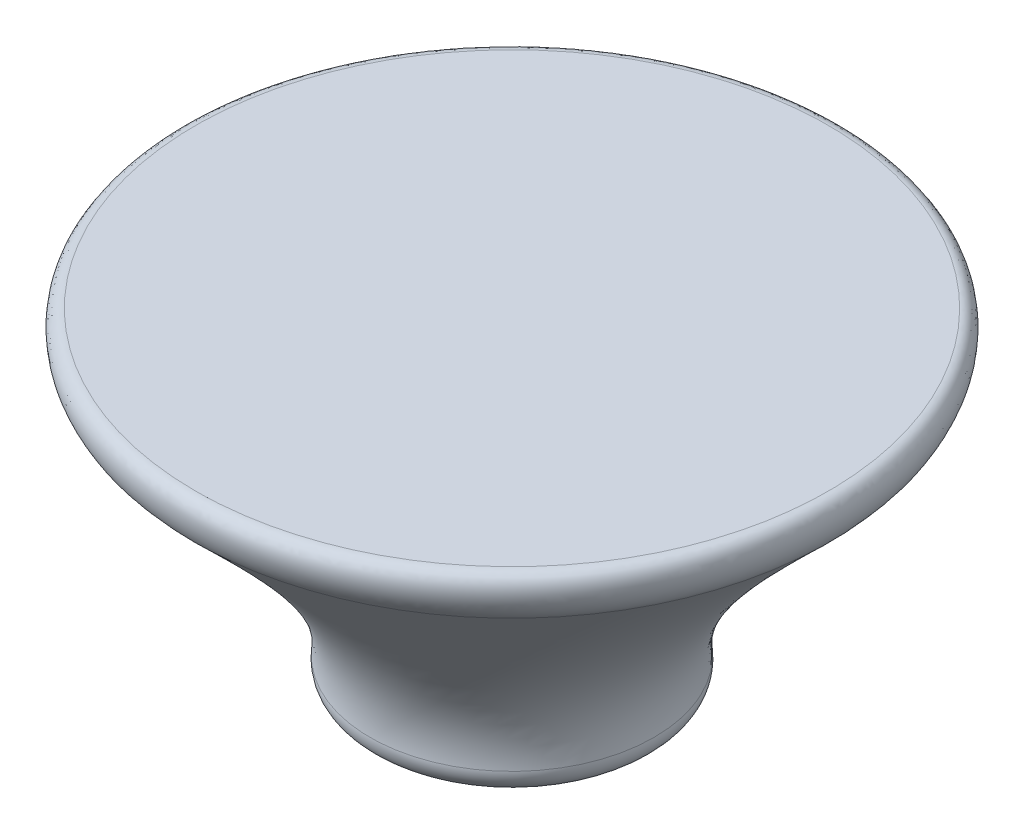
SolidWorks part; units mm, degrees
ref_plane "Front Plane" through (0, 0, 0) normal (0, 0, 1) x (1, 0, 0)
ref_plane "Top Plane" through (0, 0, 0) normal (0, 1, 0) x (1, 0, 0)
ref_plane "Right Plane" through (0, 0, 0) normal (1, 0, 0) x (0, 0, -1)
sketch "Sketch1" plane through (0, 0, 0) normal (0, 1, 0) x (1, 0, 0)
  circle A0 centre (0, 0) radius 1.8
  circle A1 centre (0, 0) radius 6.8
  dimension "D1" = 3.6
  dimension "D2" = 5
ref_plane "Plane1" through (0, 15, 0) normal (0, 1, 0) x (1, 0, 0)
sketch "Sketch2" plane through (0, 15, 0) normal (0, 1, 0) x (1, 0, 0)
  circle A0 centre (0, 0) radius 1.8 construction
  circle A1 centre (0, 0) radius 1.8
  circle A2 centre (0, 0) radius 16.8
  dimension "D1" = 15
loft "Loft1" add section "Sketch2" section "Sketch1" connector at (-3.9321, 15, -16.3333) connector at (6.3947, 0, -2.3126)
fillet "Fillet1" radius 2 1 edges at (0, 15, 16.8) second distance 0.05 first distance on face at (0, 15, 16.8)
extrude "Cut-Extrude1" cut sketch "Sketch1<3>" along normal blind 10 contours A0 region at (0, 0, 0)
sketch "Sketch1<3>" plane through (0, 0, 0) normal (0, 1, 0) x (1, 0, 0) same geometry as "Sketch1"
fillet "Fillet2" radius 1 1 edges at (0, 0, 6.8)
